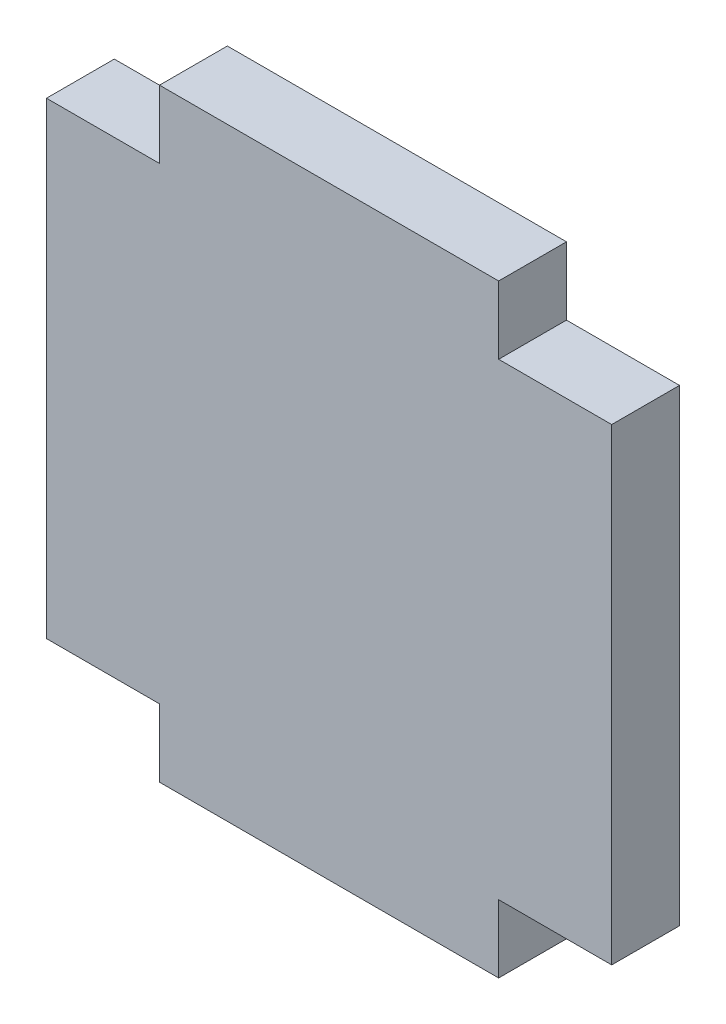
SolidWorks part; units mm, degrees
ref_plane "Plano frontal" through (0, 0, 0) normal (0, 0, 1) x (1, 0, 0)
ref_plane "Plano superior" through (0, 0, 0) normal (0, 1, 0) x (1, 0, 0)
ref_plane "Plano direito" through (0, 0, 0) normal (1, 0, 0) x (0, 0, -1)
sketch "Esboço1" plane through (0, 0, 0) normal (0, 0, 1) x (1, 0, 0)
  line L0 (12.5, 0) -> (0, 0) construction
  line L1 (-12.5, -10.35) -> (12.5, -10.35)
  line L2 (-12.5, -10.35) -> (-12.5, 10.35)
  line L3 (-12.5, 10.35) -> (12.5, 10.35)
  line L4 (12.5, -10.35) -> (12.5, 10.35)
  line L5 (-12.5, -10.35) -> (12.5, 10.35) construction
  line L6 (-12.5, 10.35) -> (12.5, -10.35) construction
  line L7 (7.5, 13.35) -> (-7.5, 13.35)
  line L8 (7.5, 13.35) -> (7.5, 10.35)
  line L9 (7.5, 10.35) -> (-7.5, 10.35)
  line L10 (-7.5, 13.35) -> (-7.5, 10.35)
  line L11 (7.5, 13.35) -> (-7.5, 10.35) construction
  line L12 (7.5, 10.35) -> (-7.5, 13.35) construction
  line L13 (7.5, -10.35) -> (-7.5, -10.35)
  line L14 (-7.5, -13.35) -> (-7.5, -10.35)
  line L15 (7.5, -13.35) -> (-7.5, -13.35)
  line L16 (7.5, -13.35) -> (7.5, -10.35)
  point P0 (0, 0)
  point P6 (0, 11.85)
  dimension "D1" = 3
  dimension "D2" = 15
  dimension "D3" = 5
  dimension "D4" = 20.7
extrude "Ressalto-extrusão1" add sketch "Esboço1" along normal blind 3 contours L1 L4 L3 L2 | L7 L10 L3 L8 | L15 L16 L1 L14 region at (0, 0, 0) region at (0, -11.85, 0) region at (0, 11.85, 0)
